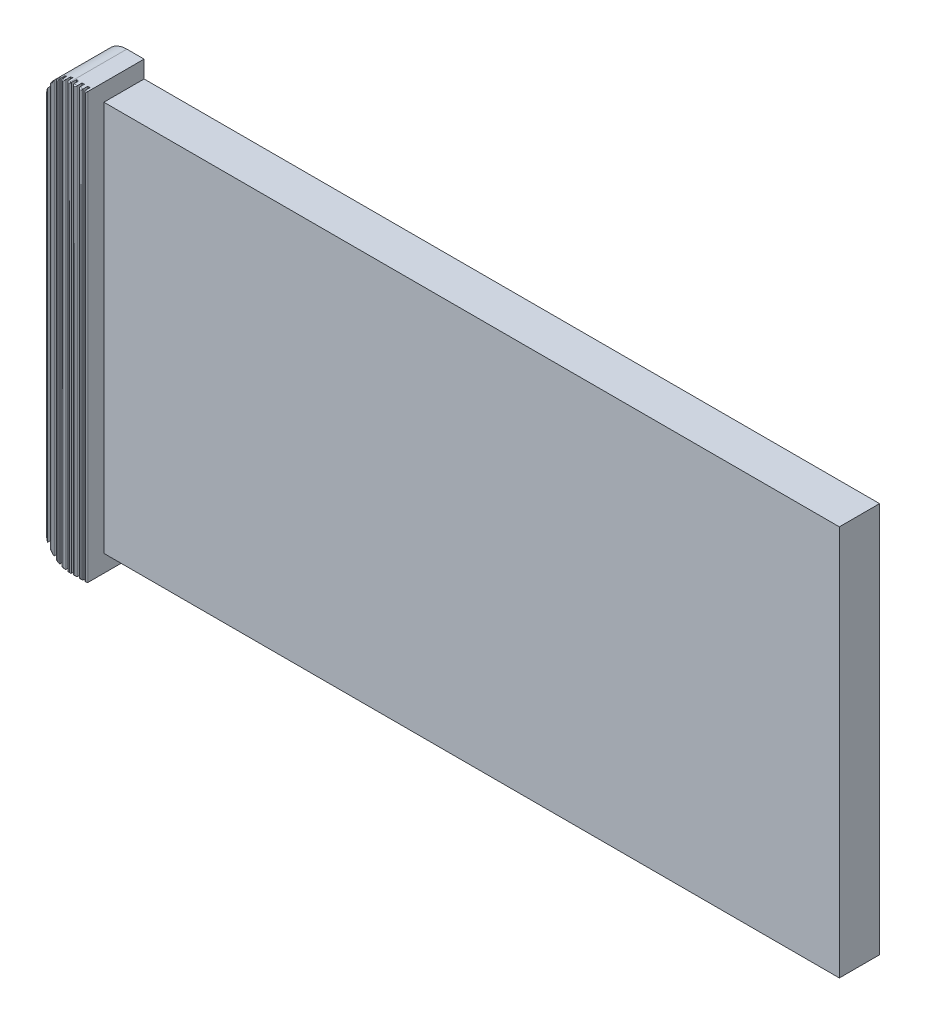
SolidWorks part; units mm, degrees
ref_plane "Alzado" through (0, 0, 0) normal (0, 0, 1) x (1, 0, 0)
ref_plane "Planta" through (0, 0, 0) normal (0, 1, 0) x (1, 0, 0)
ref_plane "Vista lateral" through (0, 0, 0) normal (1, 0, 0) x (0, 0, -1)
sketch "Croquis1" plane through (0, 0, 0) normal (0, 0, 1) x (1, 0, 0)
  line L1 (-32, 17) -> (32, 17)
  line L2 (-32, 17) -> (-32, -17)
  line L3 (-32, -17) -> (32, -17)
  line L4 (32, 17) -> (32, -17)
  line L5 (-32, 17) -> (32, -17) construction
  line L6 (-32, -17) -> (32, 17) construction
  point P0 (0, 0)
  dimension "D1" = 64
  dimension "D2" = 34
extrude "Saliente-Extruir1" add sketch "Croquis1" along normal blind 3.5
sketch "Croquis3" plane through (-32, 0, 0) normal (-1, 0, 0) x (0, 0, 1)
  line L1 (5, 18.5) -> (0, 18.5)
  line L2 (5, 18.5) -> (5, -18.5)
  line L3 (5, -18.5) -> (0, -18.5)
  line L4 (0, 18.5) -> (0, -18.5)
  point P5 (0, 0)
extrude "Saliente-Extruir2" add sketch "Croquis3" along normal blind 3.5
fillet "Redondeo1" radius 2 2 edges at (-35.5, -18.5, 2.5) (-35.5, 18.5, 2.5)
sketch "Croquis4" plane through (0, 0, 5) normal (0, 0, 1) x (1, 0, 0)
  line L1 (-32.4, 18.5) -> (-32.2, 18.5)
  line L2 (-32.4, 18.5) -> (-32.4, -18.5)
  line L3 (-32.4, -18.5) -> (-32.2, -18.5)
  line L4 (-32.2, 18.5) -> (-32.2, -18.5)
  line L5 (-33.5, 18.5) -> (-32, 18.5) construction
  line L6 (-32, 17) -> (-32, -17) construction
  line L7 (-32.9, 18.5) -> (-32.7, 18.5)
  line L8 (-32.9, 18.5) -> (-32.9, -18.5)
  line L9 (-32.9, -18.5) -> (-32.7, -18.5)
  line L10 (-32.7, 18.5) -> (-32.7, -18.5)
  line L11 (-33.4, 18.5) -> (-33.2, 18.5)
  line L12 (-33.4, 18.5) -> (-33.4, -18.5)
  line L13 (-33.4, -18.5) -> (-33.2, -18.5)
  line L14 (-33.2, 18.5) -> (-33.2, -18.5)
  line L15 (-33.9, 18.5) -> (-33.7, 18.5)
  line L16 (-33.9, 18.5) -> (-33.9, -18.5)
  line L17 (-33.9, -18.5) -> (-33.7, -18.5)
  line L18 (-33.7, 18.5) -> (-33.7, -18.5)
  line L19 (-34.4, 18.5) -> (-34.2, 18.5)
  line L20 (-34.4, 18.5) -> (-34.4, -18.5)
  line L21 (-34.4, -18.5) -> (-34.2, -18.5)
  line L22 (-34.2, 18.5) -> (-34.2, -18.5)
  line L23 (-34.9, 18.5) -> (-34.7, 18.5)
  line L24 (-34.9, 18.5) -> (-34.9, -18.5)
  line L25 (-34.9, -18.5) -> (-34.7, -18.5)
  line L26 (-34.7, 18.5) -> (-34.7, -18.5)
  line L27 (-35.4, 18.5) -> (-35.2, 18.5)
  line L28 (-35.4, 18.5) -> (-35.4, -18.5)
  line L29 (-35.4, -18.5) -> (-35.2, -18.5)
  line L30 (-35.2, 18.5) -> (-35.2, -18.5)
  dimension "D1" = 0.2
  dimension "D2" = 0.2
  dimension "D4" = 0.3
  dimension "D3" = 7
extrude "Cortar-Extruir1" cut sketch "Croquis4" against normal blind 0.5
fillet "Redondeo2" radius 0.1 30 edges at (-35.2, 0, 5) (-35.0613, 17.75, 5) (-34.9, 0, 5) (-35.0613, -17.75, 5) (-34.7, 0, 5) (-34.5541, 18.1997, 5) (-34.4, 0, 5) (-34.5541, -18.1997, 5) (-34.2, 0, 5) (-34.0517, 18.4224, 5) (-33.9, 0, 5) (-34.0517, -18.4224, 5) (-33.6001, -18.4975, 5) (-33.7, 0, 5) (-33.6001, 18.4975, 5) (-33.45, 18.5, 5) (-33.4, 0, 5) (-33.45, -18.5, 5) (-33.2, 0, 5) (-33.05, 18.5, 5) (-32.9, 0, 5) (-33.05, -18.5, 5) (-32.7, 0, 5) (-32.55, 18.5, 5) (-32.4, 0, 5) (-32.55, -18.5, 5) (-32, 0, 5) (-32.1, -18.5, 5) (-32.2, 0, 5) (-32.1, 18.5, 5)
